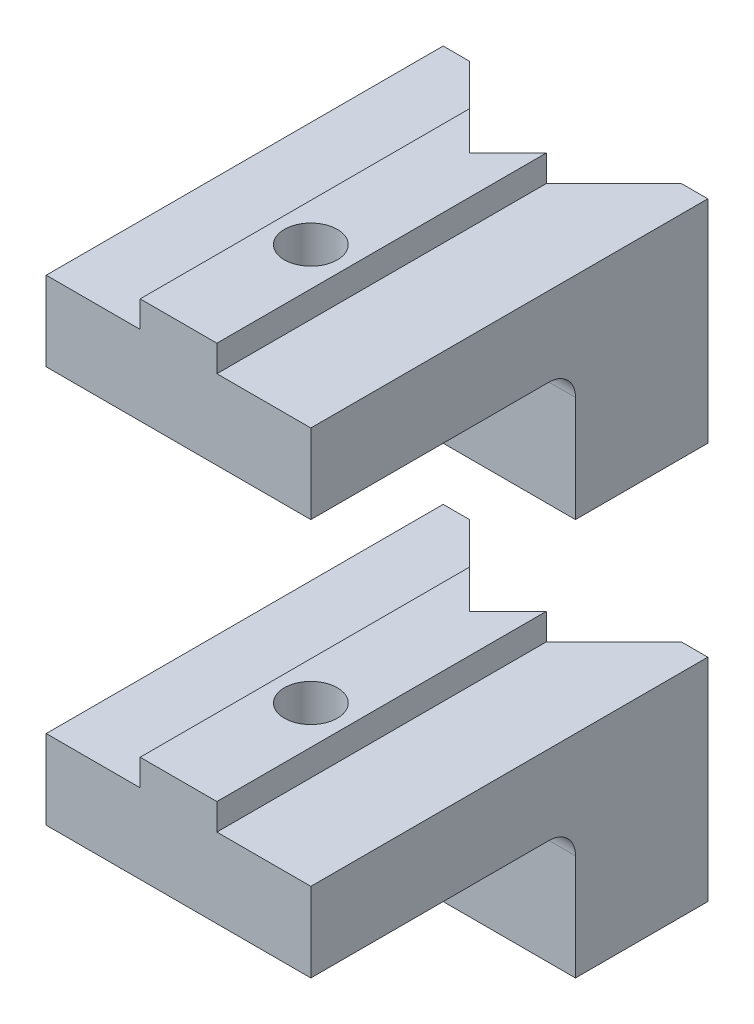
SolidWorks part; units mm, degrees
ref_plane "Front Plane" through (0, 0, 0) normal (0, 0, 1) x (1, 0, 0)
ref_plane "Top Plane" through (0, 0, 0) normal (0, 1, 0) x (1, 0, 0)
ref_plane "Right Plane" through (0, 0, 0) normal (1, 0, 0) x (0, 0, -1)
sketch "Esquisse1" plane through (0, 0, 0) normal (0, 0, 1) x (1, 0, 0)
  line L0 (-5, 0) -> (-5, 3)
  line L1 (-5, 3) -> (-1.45, 3)
  line L2 (-1.45, 3) -> (-1.45, 4)
  line L3 (-1.45, 4) -> (1.45, 4)
  line L4 (1.45, 4) -> (1.45, 3)
  line L5 (1.45, 3) -> (5, 3)
  line L6 (5, 3) -> (5, 0)
  line L7 (5, 0) -> (-5, 0)
  point P11 (0, 0)
  dimension "D1" = 10
  dimension "D2" = 3
  dimension "D3" = 1
  dimension "D4" = 2.9
  dimension "D5" = 3.55
extrude "Main" add sketch "Esquisse1" along normal blind 15
sketch "Esquisse2" plane through (0, 4, 0) normal (0, 1, 0) x (1, 0, 0)
  line L0 (0, -2.2) -> (0, 2.2) construction
  line L2 (-1.45, -15) -> (-5, -15) construction
  circle A1 centre (0, -10) radius 1
  dimension "D2" = 5
  dimension "D1" = 2
extrude "TopHole" cut sketch "Esquisse2" against normal through all
ref_axis "Axe1" through (-5.5, 0, 0) along (1, 0, 0)
sketch "Sketch1" plane through (0, 0, 0) normal (0, -1, 0) x (-1, 0, 0)
  line L0 (5, 1) -> (0, -4)
  line L1 (0, -4) -> (-5, 1)
  line L4 (-5, 1) -> (5, 1)
  line L5 (0, 2.2) -> (0, -2.2) construction
  line L7 (5, -15) -> (5, 0) construction
  line L8 (-5, -15) -> (-5, 0) construction
  line L9 (5.5, 0) -> (-5.5, 0) construction
  dimension "D1" = 1
extrude "Cut-Extrude1" cut sketch "Sketch1" against normal through all
sketch "Sketch2" plane through (0, 0, 0) normal (0, -1, 0) x (-1, 0, 0)
  line L0 (-5, 0) -> (-5, -5)
  line L1 (-5, -15) -> (-5, 0) construction
  line L2 (-5, -5) -> (5, -5)
  line L3 (5, -15) -> (5, 0) construction
  line L4 (5, -5) -> (5, 0)
  line L7 (5, 0) -> (4, 0)
  line L9 (4, 0) -> (0, -4)
  line L10 (0, 2.2) -> (0, -2.2) construction
  line L11 (0, -4) -> (4, 0) construction
  line L12 (0, -4) -> (-4, 0)
  line L13 (-4, 0) -> (-5, 0)
  line L14 (-5, -15) -> (-5, 0) construction
  line L15 (5, -15) -> (-5, -15) construction
  dimension "D1" = 10
extrude "Boss-Extrude1" add sketch "Sketch2" along normal blind 5
fillet "Fillet1" radius 1 1 edges at (0, 0, 5)
pattern_linear "LPattern1" count 2 spacing 15 along (0, 1, 0) of bodies 116
